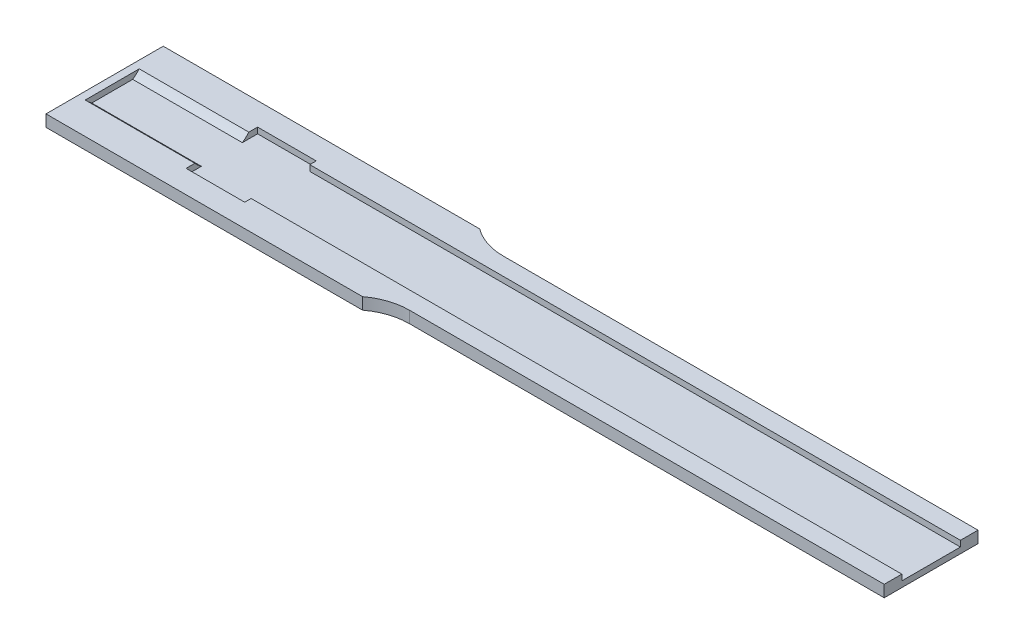
SolidWorks part; units mm, degrees
ref_plane "Front Plane" through (0, 0, 0) normal (0, 0, 1) x (1, 0, 0)
ref_plane "Top Plane" through (0, 0, 0) normal (0, 1, 0) x (1, 0, 0)
ref_plane "Right Plane" through (0, 0, 0) normal (1, 0, 0) x (0, 0, -1)
sketch "Sketch1" plane through (0, 0, 0) normal (0, 1, 0) x (1, 0, 0)
  line L0 (-32.4167, 0) -> (142.483, 0) construction
  line L3 (0, 10) -> (141, 10)
  line L4 (141, 10) -> (141, -10)
  line L5 (141, -10) -> (0, -10)
  line L8 (0, 10) -> (0, -10)
  line L9 (-4, 7.5) -> (0, 7.5)
  line L10 (-4, -7.5) -> (0, -7.5)
  circle A0 centre (-4, 0) radius 2
  arc A1 (-4, 7.5) -> (-4, -7.5) centre (-4, 0) ccw
  point P15 (141, 0)
  dimension "D1" = 4
  dimension "D2" = 4
  dimension "D3" = 145
  dimension "D5" = 7.5
  dimension "D4" = 20
extrude "Boss-Extrude1" add sketch "Sketch1" along normal mid plane 8 contours A1 L0 A0 L8 L3 | L0 A1 L5 L8 A0 region at (-5.1875, 0, -3.6496) region at (-5.1875, 0, 3.6496)
extrude "Boss-Extrude2" add sketch "Sketch1<3>" along normal mid plane 12 contours L8 L0 L4 L3 | L0 L8 L5 L4 region at (70.5, 0, -5) region at (70.5, 0, 5)
sketch "Sketch1<3>" plane through (0, 0, 0) normal (0, 1, 0) x (1, 0, 0) same geometry as "Sketch1"
sketch "Sketch3" plane through (0, 0, 0) normal (-1, 0, 0) x (0, 0, 1)
  line L0 (-3.4943, -5) -> (3.4943, -5)
  line L1 (-6.1, 0) -> (-6.1, 6)
  line L2 (-10, 6) -> (10, 6) construction
  line L3 (-6.1, 6) -> (6.1, 6)
  line L4 (6.1, 6) -> (6.1, 0)
  arc A0 (3.4943, -5) -> (6.1, 0) centre (0, 0) ccw
  arc A1 (-6.1, 0) -> (-3.4943, -5) centre (0, 0) ccw
  dimension "D1" = 12.2
  dimension "D2" = 5
extrude "Cut-Extrude1" cut sketch "Sketch3" against normal blind 18 from offset 2 offset against normal yes
sketch "Sketch4" plane through (20, 0, 0) normal (-1, 0, 0) x (0, 0, 1)
  line L0 (-6.1, 6) -> (-6.1, -5)
  line L1 (-6.1, -5) -> (6.1, -5)
  line L2 (6.1, -5) -> (6.1, 6)
  line L3 (6.1, 6) -> (-6.1, 6)
  dimension "D1" = 11
extrude "Cut-Extrude2" cut sketch "Sketch4" against normal blind 10
sketch "Sketch5" plane through (0, 0, 0) normal (-1, 0, 0) x (0, 0, 1)
  line L1 (-10, -6) -> (10, -6)
  line L2 (-10, -6) -> (-10, -8)
  line L3 (-10, -8) -> (10, -8)
  line L4 (10, -6) -> (10, -8)
  dimension "D1" = 20
  dimension "D2" = 2
extrude "Boss-Extrude3" add sketch "Sketch5" against normal blind 35
sketch "Sketch9" plane through (2, 0, 0) normal (1, 0, 0) x (0, 0, -1)
  line L0 (3.4943, -5) -> (-3.4943, -5) construction
  line L1 (3.4943, -5) -> (-3.4943, -5)
  line L2 (6.1, 0) -> (-6.1, 0) construction
  line L3 (3.4943, 5) -> (-3.4943, 5)
  arc A0 (3.4943, -5) -> (6.1, 0) centre (0, 0) ccw construction
  arc A1 (-6.1, 0) -> (-3.4943, -5) centre (0, 0) ccw construction
  arc A2 (3.4943, -5) -> (3.4943, 5) centre (0, 0) ccw
  arc A3 (-3.4943, 5) -> (-3.4943, -5) centre (0, 0) ccw
extrude "Cut-Extrude4" cut sketch "Sketch9" against normal blind 0.7
sketch "Sketch11" plane through (0, 0, 0) normal (0, 1, 0) x (1, 0, 0)
  line L0 (2, -6.1) -> (2, 6.1) construction
  line L2 (2, 1) -> (2, -1)
  line L4 (0, 10) -> (0, -10) construction
  line L5 (0, -3) -> (0, -7.5)
  line L6 (0, 7.5) -> (0, -7.5) construction
  line L7 (0, -7.5) -> (-2, -7.5)
  line L8 (-4, -7.5) -> (0, -7.5) construction
  line L9 (-2, -7.5) -> (-2, -3)
  arc A0 (2, -1) -> (0, -3) centre (2, -3) ccw
  arc A1 (2, 1) -> (-2, -3) centre (2, -3) ccw
  dimension "D1" = 2
  dimension "D2" = 2
  dimension "D3" = 1
extrude "Cut-Extrude5" cut sketch "Sketch11" against normal mid plane 2 contours A0 L5 L7 L9 A1 L2
sketch "Sketch12" plane through (0, 6, 0) normal (0, 1, 0) x (1, 0, 0)
  line L0 (54, 10) -> (54, 8)
  line L1 (0, 10) -> (141, 10) construction
  line L2 (54, 8) -> (141, 8)
  line L3 (141, 10) -> (141, -10) construction
  line L4 (54, -10) -> (54, -8)
  line L5 (141, -10) -> (0, -10) construction
  line L6 (54, -8) -> (141, -8)
  line L7 (54, 10) -> (141, 10)
  line L8 (141, 10) -> (141, 8)
  line L9 (141, -8) -> (141, -10)
  line L10 (141, -10) -> (54, -10)
  dimension "D1" = 16
  dimension "D2" = 2
  dimension "D3" = 87
extrude "Cut-Extrude6" cut sketch "Sketch12" against normal up to next
fillet "Fillet1" radius 10 2 edges at (54, 0, 8) (54, 0, -8)
sketch "Sketch13" plane through (30, 0, 0) normal (-1, 0, 0) x (0, 0, 1)
  line L4 (-5, 5) -> (-5, 1)
  line L6 (-5, 1) -> (-3.5, 1)
  line L7 (-3.5, 1) -> (-3.5, -1)
  line L8 (-3.5, -1) -> (-5, -1)
  line L9 (-5, -1) -> (-5, -5)
  line L12 (-5, -5) -> (5, -5)
  line L15 (5, -5) -> (5, -1)
  line L16 (5, -1) -> (3.5, -1)
  line L17 (3.5, -1) -> (3.5, 1)
  line L18 (3.5, 1) -> (5, 1)
  line L19 (5, 1) -> (5, 5)
  line L20 (5, 5) -> (-5, 5)
  line L21 (0, 8.1097) -> (0, -11.293) construction
  point P15 (-3.5, 0)
  point P23 (0, -5)
  point P24 (0, 5)
  dimension "D1" = 4
  dimension "D2" = 5
  dimension "D3" = 2
  dimension "D4" = 1.5
  dimension "D5" = 10
  dimension "D6" = 1.5
extrude "Cut-Extrude7" cut sketch "Sketch13" against normal through all
sketch "Sketch14" plane through (0, 0, 0) normal (-1, 0, 0) x (0, 0, 1)
  line L0 (10, 6) -> (10, -8) construction
  line L1 (-10, 6) -> (10, 6)
  line L2 (-10, 6) -> (-10, 4)
  line L3 (-10, 4) -> (10, 4)
  line L4 (10, 6) -> (10, 4)
  dimension "D1" = 2
extrude "Cut-Extrude8" cut sketch "Sketch14" against normal through all
fillet "Fillet2" radius 10 1 edges at (35, -6, 0)
sketch "Sketch15" plane through (0, 0, 0) normal (1, 0, 0) x (0, 0, -1)
  line L1 (10, -4) -> (-10, -4)
  line L2 (10, -4) -> (10, 4)
  line L3 (10, 4) -> (-10, 4)
  line L4 (-10, -4) -> (-10, 4)
  line L5 (10, -4) -> (-10, 4) construction
  line L6 (10, 4) -> (-10, -4) construction
  point P0 (0, 0)
extrude "Cut-Extrude9" cut sketch "Sketch15" along normal through all and the other way through all
sketch "Sketch16" plane through (0, 0, 0) normal (1, 0, 0) x (0, 0, -1)
  line L1 (-10, -8) -> (10, -8)
  line L2 (-10, -8) -> (-10, -6)
  line L3 (-10, -6) -> (10, -6)
  line L4 (10, -8) -> (10, -6)
extrude "Cut-Extrude10" cut sketch "Sketch16" along normal up to next
